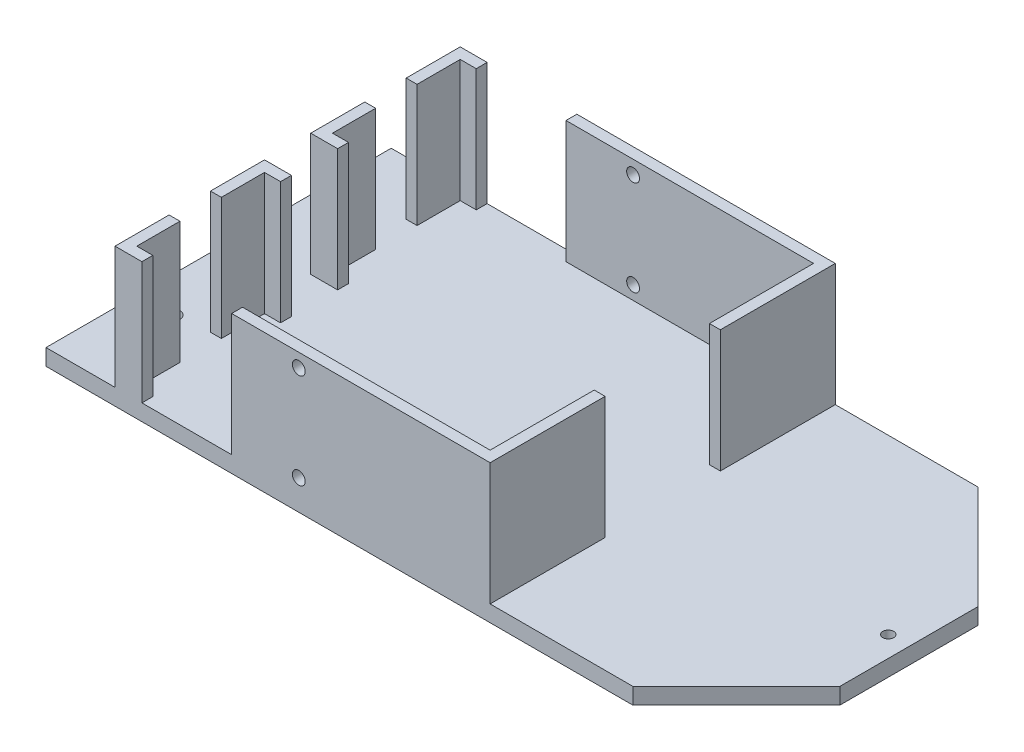
SolidWorks part; units mm, degrees
ref_plane "Front Plane" through (0, 0, 0) normal (0, 0, 1) x (1, 0, 0)
ref_plane "Top Plane" through (0, 0, 0) normal (0, 1, 0) x (1, 0, 0)
ref_plane "Right Plane" through (0, 0, 0) normal (1, 0, 0) x (0, 0, -1)
sketch "Sketch1" plane through (0, 0, 0) normal (0, 1, 0) x (1, 0, 0)
  line L1 (-63.5, 31.75) -> (63.5, 31.75)
  line L2 (-63.5, 31.75) -> (-63.5, -31.75)
  line L3 (-63.5, -31.75) -> (63.5, -31.75)
  line L4 (63.5, 31.75) -> (63.5, -31.75)
  line L5 (-63.5, 31.75) -> (63.5, -31.75) construction
  line L6 (-63.5, -31.75) -> (63.5, 31.75) construction
  point P0 (0, 0)
  dimension "D1" = 63.5
  dimension "D2" = 127
extrude "Boss-Extrude1" add sketch "Sketch1" along normal blind 3
sketch "Sketch2" plane through (0, 3, 0) normal (0, 1, 0) x (1, 0, 0)
  line L0 (-61.5, 29.75) -> (-63.5, 29.75)
  line L1 (-63.5, 31.75) -> (63.5, 31.75)
  line L2 (-63.5, 31.75) -> (-63.5, -31.75)
  line L3 (-63.5, -31.75) -> (63.5, -31.75)
  line L4 (63.5, 31.75) -> (63.5, -31.75)
  line L5 (-63.5, 31.75) -> (63.5, -31.75) construction
  line L6 (-63.5, -31.75) -> (63.5, 31.75) construction
  line L7 (-61.5, 29.75) -> (61.5, 29.75)
  line L8 (-61.5, 29.75) -> (-61.5, -29.75)
  line L9 (-61.5, -29.75) -> (61.5, -29.75)
  line L10 (61.5, 29.75) -> (61.5, -29.75)
  line L11 (-61.5, 29.75) -> (61.5, -29.75) construction
  line L12 (-61.5, -29.75) -> (61.5, 29.75) construction
  line L13 (-61.5, -29.75) -> (-63.5, -29.75)
  point P0 (0, 0)
  point P7 (0, 0)
  line M5 (63.5, -31.75) -> (63.5, 31.75)
  line M6 (63.5, 31.75) -> (-63.5, 31.75)
  line M7 (-63.5, 31.75) -> (-63.5, -31.75)
  line M8 (-63.5, -31.75) -> (63.5, -31.75)
  dimension "D1" = 2
  dimension "D2" = 2
extrude "Boss-Extrude2" add sketch "Sketch2" along normal blind 22.5 contours L9 L13 L2 L0 L7 L10 M8 M5 M6 M7 region at (-62.5, 3, -31.1699)
sketch "Sketch3" plane through (61.5, 0, 0) normal (-1, 0, 0) x (0, 0, 1)
  line L0 (29.75, 3) -> (-29.75, 3) construction
  line L1 (-7.62, 25.5) -> (7.62, 25.5)
  line L2 (-7.62, 25.5) -> (-7.62, 3)
  line L3 (-7.62, 3) -> (7.62, 3)
  line L4 (7.62, 25.5) -> (7.62, 3)
  line L5 (-7.62, 25.5) -> (7.62, 3) construction
  line L6 (-7.62, 3) -> (7.62, 25.5) construction
  line L8 (0, -55) -> (0, 55) construction
  line L9 (-29.75, 25.5) -> (29.75, 25.5) construction
  point P0 (0, 14.25)
  dimension "D1" = 7.62
extrude "Cut-Extrude1" cut sketch "Sketch3" against normal through all
sketch "Sketch4" plane through (0, 3, 0) normal (0, 1, 0) x (1, 0, 0)
  line L0 (-63.5, -29.75) -> (61.5, -29.75) construction
  line L1 (-48.8, -29.75) -> (16.2, -29.75)
  line L2 (-48.8, -29.75) -> (-48.8, -6.25)
  line L3 (-48.8, -6.25) -> (16.2, -6.25)
  line L4 (16.2, -29.75) -> (16.2, -6.25)
  line L5 (-50.8, -4.25) -> (18.2, -4.25)
  line L6 (18.2, -31.75) -> (18.2, -4.25)
  line L7 (-50.8, -31.75) -> (18.2, -31.75)
  line L8 (-50.8, -31.75) -> (-50.8, -4.25)
  line L9 (-55, 0) -> (55, 0) construction
  line L10 (-50.8, 31.75) -> (-50.8, 4.25)
  line L11 (-50.8, 31.75) -> (18.2, 31.75)
  line L12 (18.2, 31.75) -> (18.2, 4.25)
  line L13 (-50.8, 4.25) -> (18.2, 4.25)
  line L14 (16.2, 29.75) -> (16.2, 6.25)
  line L15 (-48.8, 6.25) -> (16.2, 6.25)
  line L16 (-48.8, 29.75) -> (-48.8, 6.25)
  line L17 (-48.8, 29.75) -> (16.2, 29.75)
  line L18 (-63.5, 29.75) -> (-63.5, -29.75) construction
  line L19 (5.5, -4.25) -> (5.5, -6.25)
  line L20 (-50.8, -14.19) -> (-48.8, -14.19)
  line L21 (-50.8, -21.81) -> (-48.8, -21.81)
  line L22 (-49.8, -14.19) -> (-49.8, -21.81) construction
  line L23 (-50.8, 21.81) -> (-48.8, 21.81)
  line L24 (-50.8, 14.19) -> (-48.8, 14.19)
  line L25 (16.2, -10.6) -> (18.2, -10.6)
  line L26 (5.5, 4.25) -> (5.5, 6.25)
  line L27 (16.2, 10.6) -> (18.2, 10.6)
  point P31 (-49.8, -18)
  point P32 (-48.8, -18)
  line M3 (-63.5, -29.75) -> (61.5, -29.75)
  line M9 (61.5, 29.75) -> (-63.5, 29.75)
  dimension "D1" = 23.5
  dimension "D2" = 65
  dimension "D3" = 12.7
  dimension "D5" = 7.62
  dimension "D6" = 12.7
  dimension "D7" = 6.35
  dimension "D4" = 2
extrude "Boss-Extrude4" add sketch "Sketch4" along normal up to surface (22.5 mm away) contours L24 L10 L13 L12 L14 L15 L16 M9 | L10 L23 L16 M9 | L21 L8 L2 M3 | L8 L20 L2 L3 L4 L6 L5 M3 | L25 L4 L6 M3 | L14 L27 L12 M9 region at (-49.8, 3, 25.78) region at (17.2, 3, 20.175) region at (-26.0057, 3, 5.8643) region at (-49.8, 3, -25.78) region at (-26.0057, 3, -5.8643) region at (17.2, 3, -20.175) up to face at (20.5, 25.5, -23.04)
sketch "Sketch5" plane through (0, 0, 29.75) normal (0, 0, -1) x (-1, 0, 0)
  line L1 (29.345, 25.5) -> (45.855, 25.5)
  line L2 (29.345, 25.5) -> (29.345, 3)
  line L3 (29.345, 3) -> (45.855, 3)
  line L4 (45.855, 25.5) -> (45.855, 3)
  line L5 (29.345, 25.5) -> (45.855, 3) construction
  line L6 (29.345, 3) -> (45.855, 25.5) construction
  line L9 (48.8, 3) -> (-16.2, 3) construction
  line L10 (63.5, 25.5) -> (-63.5, 25.5) construction
  point P0 (37.6, 14.25)
  dimension "D1" = 11.2
  dimension "D2" = 16.51
extrude "Cut-Extrude2" cut sketch "Sketch5" against normal through all and the other way through all
sketch "Sketch6" plane through (0, 25.5, 0) normal (0, 1, 0) x (1, 0, 0)
  line L0 (18.2, 29.75) -> (18.2, 31.75)
  line L1 (63.5, 31.75) -> (-29.345, 31.75) construction
  line L2 (18.2, -29.75) -> (18.2, -31.75)
  line L3 (-29.345, -31.75) -> (63.5, -31.75) construction
  line L4 (18.2, -31.75) -> (63.5, -31.75)
  line L5 (63.5, -31.75) -> (63.5, -7.62)
  line L6 (63.5, -7.62) -> (61.5, -7.62)
  line L7 (61.5, -7.62) -> (61.5, -29.75)
  line L8 (61.5, -29.75) -> (18.2, -29.75)
  line L9 (18.2, 31.75) -> (63.5, 31.75)
  line L10 (63.5, 31.75) -> (63.5, 7.62)
  line L11 (63.5, 7.62) -> (61.5, 7.62)
  line L12 (61.5, 7.62) -> (61.5, 29.75)
  line L13 (61.5, 29.75) -> (18.2, 29.75)
  line L14 (-63.5, 31.75) -> (-63.5, 29.75)
  line L15 (-63.5, 29.75) -> (-50.8, 29.75)
  line L16 (-50.8, 29.75) -> (-50.8, 31.75)
  line L17 (-45.855, 31.75) -> (-63.5, 31.75) construction
  line L18 (-50.8, 31.75) -> (-63.5, 31.75)
  line L19 (-63.5, -29.75) -> (-63.5, -31.75)
  line L20 (-63.5, -29.75) -> (-50.8, -29.75)
  line L22 (-50.8, -29.75) -> (-50.8, -31.75)
  line L23 (-63.5, -31.75) -> (-45.855, -31.75) construction
  line L24 (-50.8, -31.75) -> (-63.5, -31.75)
extrude "Cut-Extrude3" cut sketch "Sketch6" against normal up to surface (22.5 mm away) up to face at (-48.485, 3, -8.23)
sketch "Sketch8" plane through (0, 0, 31.75) normal (0, 0, 1) x (1, 0, 0)
  line L0 (-29.345, 3) -> (18.2, 3)
  line L1 (-17, 3) -> (-17, 25.5) construction
  line L2 (-29.345, 25.5) -> (18.2, 25.5) construction
  line L3 (-48.8, 3) -> (-48.8, 25.5) construction
  circle A0 centre (-17, 23) radius 1.1811
  circle A1 centre (-17, 5.5) radius 1.1811
  point P10 (-17, 5.5)
  point P11 (-17, 23)
  dimension "D4" = 2.3622
  dimension "D1" = 31.8
  dimension "D2" = 17.5
  dimension "D3" = 2.5
extrude "Cut-Extrude4" cut sketch "Sketch8" against normal through all contours A0 L1 | L1 A0 | A1 L1 | L1 A1 region at (-17.5013, 5.5, 31.75) region at (-17.5013, 23, 31.75) region at (-16.4987, 23, 31.75) region at (-16.4987, 5.5, 31.75)
sketch "Sketch10" plane through (0, 0, 0) normal (0, -1, 0) x (1, 0, 0)
  line L0 (44.45, 31.75) -> (63.5, 12.7)
  line L1 (-63.5, 31.75) -> (63.5, 31.75) construction
  line L2 (63.5, 31.75) -> (63.5, -31.75) construction
  line L3 (63.5, 12.7) -> (63.5, -12.7)
  line L4 (63.5, -12.7) -> (44.45, -31.75)
  line L5 (63.5, -31.75) -> (-63.5, -31.75) construction
  line L6 (14.025, 0) -> (-14.025, 0) construction
  line L9 (44.45, 31.75) -> (63.5, 31.75)
  line L10 (63.5, 31.75) -> (63.5, 12.7)
  line L11 (63.5, -12.7) -> (63.5, -31.75)
  line L12 (63.5, -31.75) -> (44.45, -31.75)
  point P6 (63.5, 0)
  point P17 (59.69, 0)
  line M3 (63.5, -31.75) -> (63.5, 31.75)
  line M4 (63.5, 31.75) -> (-63.5, 31.75)
  line M6 (-63.5, -31.75) -> (63.5, -31.75)
  dimension "D1" = 25.4
  dimension "D2" = 3.81
  dimension "D3" = 45
  dimension "D4" = 45
extrude "Cut-Extrude5" cut sketch "Sketch10" against normal through all contours L0 M4 M3 | L4 M3 M6 region at (57.15, 0, 25.4) region at (57.15, 0, -25.4)
hole_wizard "Ø2.0mm Dowel Hole1" positions "3DSketch1" profile "Sketch12" hole size "Ø2.0" standard "ANSI Metric" end condition through all
sketch3d "3DSketch1"
  point P2 (59.69, 0, 0)
sketch "Sketch12" plane through (59.69, 0, 0) normal (1, 0, 0) x (0, 0, -1)
  line L0 (0, 0) -> (0, 25.5)
  line L1 (0, 25.5) -> (1, 25.5)
  line L2 (1, 25.5) -> (1, 0)
  line L5 (1, 0) -> (0, 0)
  line L11 (0, -6.35) -> (0, 107.95) construction
  dimension "Thru Hole Dia." = 2
  dimension "Thru Hole Depth" = 25.5
sketch "Sketch13" plane through (0, 0, 6.25) normal (0, 0, 1) x (1, 0, 0)
  line L0 (-29.345, 25.5) -> (-29.345, 3)
  line L1 (-29.345, 25.5) -> (5.5, 25.5)
  line L2 (5.5, 25.5) -> (5.5, 3)
  line L3 (5.5, 3) -> (-29.345, 3)
extrude "Cut-Extrude6" cut sketch "Sketch13" against normal up to surface (12.5 mm away) up to face at (-18.1811, 23, -6.25)
sketch "Sketch14" plane through (0, 3, 0) normal (0, 1, 0) x (1, 0, 0)
  line L0 (-63.5, 31.75) -> (-63.5, -31.75) construction
  line L1 (-63.5, 15) -> (-57.15, 15)
  line L2 (-63.5, 15) -> (-63.5, -15)
  line L3 (-63.5, -15) -> (-57.15, -15)
  line L4 (-57.15, 15) -> (-57.15, -15)
  line L5 (-14.025, 0) -> (14.025, 0) construction
  point P6 (-57.15, 0)
  dimension "D1" = 30
  dimension "D2" = 6.35
hole_wizard "Ø3.0mm Dowel Hole1" positions "3DSketch2" profile "Sketch15" hole size "Ø3.0" standard "ANSI Metric" end condition through all
sketch3d "3DSketch2"
  point P0 (-57.15, 3, -15)
  point P3 (-57.15, 3, 15)
sketch "Sketch15" plane through (-57.15, 3, -15) normal (1, 0, 0) x (0, 0, 1)
  line L0 (0, 0) -> (0, 3)
  line L1 (0, 3) -> (1.5, 3)
  line L2 (1.5, 3) -> (1.5, 0)
  line L5 (1.5, 0) -> (0, 0)
  line L11 (0, -6.35) -> (0, 107.95) construction
  dimension "Thru Hole Dia." = 3
  dimension "Thru Hole Depth" = 3
